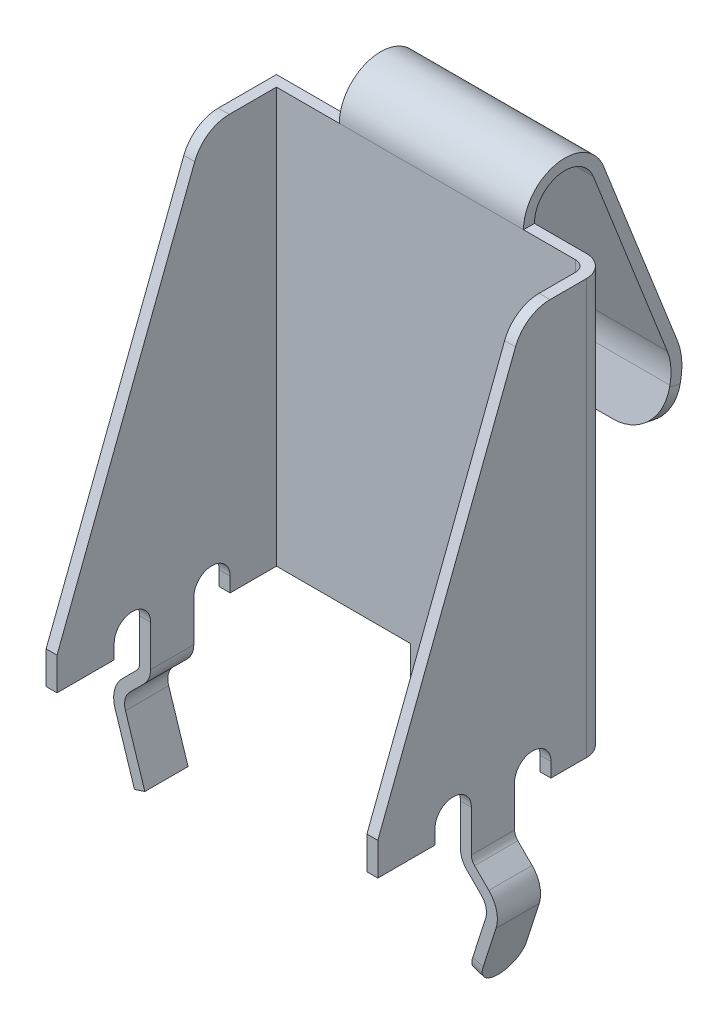
SolidWorks part; units mm, degrees
ref_plane "Front Plane" through (0, 0, 0) normal (0, 0, 1) x (1, 0, 0)
ref_plane "Top Plane" through (0, 0, 0) normal (0, 1, 0) x (1, 0, 0)
ref_plane "Right Plane" through (0, 0, 0) normal (1, 0, 0) x (0, 0, -1)
sketch "Sketch1" plane through (0, 0, 0) normal (0, 1, 0) x (1, 0, 0)
  line L1 (4.565, 0.15) -> (-4.565, 0.15)
  line L2 (4.565, 0.15) -> (4.565, -0.15)
  line L3 (4.565, -0.15) -> (-4.565, -0.15)
  line L4 (-4.565, 0.15) -> (-4.565, -0.15)
  line L5 (4.565, 0.15) -> (-4.565, -0.15) construction
  line L6 (4.565, -0.15) -> (-4.565, 0.15) construction
  point P0 (0, 0)
  dimension "D1" = 0.3
  dimension "D2" = 9.13
extrude "Boss-Extrude1" add sketch "Sketch1" along normal blind 11.42
sketch "Sketch2" plane through (0, 0, 0) normal (1, 0, 0) x (0, 0, -1)
  line L0 (-0.15, 11.42) -> (0.15, 11.42)
  line L1 (1.7718, 11.7271) -> (3.8061, 6.5484)
  line L2 (2.0511, 11.8368) -> (4.0854, 6.6581)
  line L3 (3.8797, 5.7002) -> (3.6104, 4.38)
  line L4 (3.6104, 4.38) -> (3.9044, 4.32)
  line L5 (3.9044, 4.32) -> (4.1737, 5.6403)
  line L6 (0.15, 11.42) -> (0.15, 0) construction
  line L7 (-0.15, 11.42) -> (-0.15, 0) construction
  line L8 (-0.15, 12.56) -> (2.8616, 12.56) construction
  line L9 (4.21, 11.1436) -> (4.21, 7.449) construction
  arc A0 (0.15, 11.42) -> (1.7718, 11.7271) centre (0.99, 11.42) cw
  arc A1 (-0.15, 11.42) -> (2.0511, 11.8368) centre (0.99, 11.42) cw
  arc A2 (3.8061, 6.5484) -> (3.8797, 5.7002) centre (2.41, 6) cw
  arc A3 (4.0854, 6.6581) -> (4.1737, 5.6403) centre (2.41, 6) cw
  point P9 (4.0992, 5.7403)
  point P22 (1.7542, 11.7687)
  point P25 (3.8176, 7.449)
  point P27 (3.8033, 6.4934)
  point P28 (0, 0)
  point P29 (3.9044, 6.1297)
  point P30 (0, 0)
  point P31 (0, 0)
  point P32 (0, 0)
  dimension "D1" = 1.14
  dimension "D5" = 1.5
  dimension "D2" = 4.06
  dimension "D3" = 4.32
  dimension "D4" = 6
extrude "Boss-Extrude2" add sketch "Sketch2" along normal mid plane 5.07
fillet "Fillet1" radius 1.3 2 edges at (-2.535, 4.35, -3.7574) (2.535, 4.35, -3.7574)
sketch "Sketch3" plane through (0, 0, -0.15) normal (0, 0, -1) x (-1, 0, 0)
  line L0 (-0.57, 0) -> (0.57, 0)
  line L1 (-4.565, 0) -> (4.565, 0) construction
  line L2 (0.57, 0) -> (0.57, -1.6)
  line L3 (0.57, -1.6) -> (0.33, -2.7708)
  line L4 (-0.57, 0) -> (-0.57, -1.6)
  line L5 (-0.57, -1.6) -> (-0.33, -2.7708)
  arc A0 (-0.33, -2.7708) -> (0.33, -2.7708) centre (0, -2.7031) ccw
  point P3 (-0.57, -1.5246)
  point P6 (0, 0)
  point P12 (0, -3.04)
  point P13 (0.57, -1.5959)
  point P14 (0.2485, -2.812)
  point P15 (0, 0)
  point P16 (0, 0)
  point P17 (0, 0)
  point P18 (0, 0)
  point P19 (-0.57, -1.6758)
  point P20 (0.332, -2.7687)
  dimension "D1" = 1.14
  dimension "D2" = 3.04
  dimension "D3" = 1.6
  dimension "D4" = 0.66
extrude "Boss-Extrude3" add sketch "Sketch3" against normal up to surface (0.3 mm away) up to face at (0, 7.6133, 0.15)
sketch "Sketch4" plane through (4.565, 0, 0) normal (1, 0, 0) x (0, 0, -1)
  line L0 (-0.15, 11.42) -> (-0.15, 0)
  line L1 (-0.15, 0) -> (-1.425, 0)
  line L2 (-0.15, 11.42) -> (-1.45, 11.42)
  line L3 (-2.4, 10.7672) -> (-6.19, 0.9)
  line L4 (-6.19, 0.9) -> (-6.19, 0)
  line L5 (-3.615, 0) -> (-2.425, 0)
  line L6 (-1.425, 0) -> (-1.425, 0.4)
  line L7 (-2.425, 0.4) -> (-2.425, 0)
  line L8 (-3.615, 0) -> (-3.615, 0.4)
  line L9 (-4.615, 0.4) -> (-4.615, 0)
  line L10 (-4.615, 0) -> (-6.19, 0)
  line L11 (0.15, 11.42) -> (0.15, 0) construction
  arc A0 (-1.45, 11.42) -> (-2.4, 10.7672) centre (-1.45, 10.4023) ccw
  arc A1 (-1.425, 0.4) -> (-2.425, 0.4) centre (-1.925, 0.4) ccw
  arc A2 (-3.615, 0.4) -> (-4.615, 0.4) centre (-4.115, 0.4) ccw
  point P9 (-3.02, 0)
  point P11 (0, 0)
  point P20 (-1.425, 0.4)
  point P24 (-5.8578, 0.0655)
  point P27 (-6.19, 1.692)
  point P28 (-4.115, 0.9)
  point P29 (-1.4501, 11.42)
  point P30 (-6.19, 0.9)
  point P31 (-3.615, 0.4)
  point P32 (-4.615, 0)
  point P33 (0, 0)
  point P34 (-4.115, 0.4)
  point P35 (-3.615, 0)
  point P36 (-3.615, 0.4)
  point P37 (-1.425, 0.4)
  point P38 (-1.45, 11.42)
  point P39 (-6.19, 0.9)
  point P40 (-4.615, 0)
  point P41 (-4.615, 0.4)
  point P42 (-3.615, 0.4)
  point P43 (-2.425, 0.4)
  point P44 (-1.425, 0.4)
  point P45 (-2.425, 0)
  point P46 (-3.615, 0)
  point P47 (-1.45, 11.42)
  dimension "D1" = 3.17
  dimension "D3" = 1
  dimension "D5" = 6.34
  dimension "D2" = 1.19
  dimension "D4" = 0.4
  dimension "D6" = 1.3
  dimension "D7" = 2.25
extrude "Boss-Extrude4" add sketch "Sketch4" against normal blind 0.3
fillet "Fillet2" radius 0.3 1 edges at (4.265, 5.71, 0.15)
fillet "Fillet3" radius 0.6 1 edges at (4.565, 5.71, -0.15)
ref_plane "Plane1" through (0, 0, 3.02) normal (0, 0, -1) x (-1, 0, 0)
sketch "Sketch5" plane through (0, 0, 3.02) normal (0, 0, -1) x (-1, 0, 0)
  line L0 (-4.565, 0) -> (-4.265, 0)
  line L1 (-4.565, 0) -> (-4.565, -0.7344)
  line L2 (-4.265, 0) -> (-4.265, -0.7344)
  line L3 (-4.6529, -0.9465) -> (-5.0457, -1.3393)
  line L4 (-4.4407, -1.1586) -> (-4.8336, -1.5514)
  line L5 (-5.2416, -2.1499) -> (-4.7078, -3.81)
  line L6 (-4.7078, -3.81) -> (-4.4222, -3.7182)
  line L7 (-4.4222, -3.7182) -> (-4.956, -2.0581)
  line L8 (-5.28, -1.8087) -> (-5.28, -4.8094) construction
  arc A0 (-4.565, -0.7344) -> (-4.6529, -0.9465) centre (-4.865, -0.7344) cw
  arc A1 (-4.265, -0.7344) -> (-4.4407, -1.1586) centre (-4.865, -0.7344) cw
  arc A2 (-4.8336, -1.5514) -> (-4.956, -2.0581) centre (-4.48, -1.905) ccw
  arc A3 (-5.0457, -1.3393) -> (-5.2416, -2.1499) centre (-4.48, -1.905) ccw
  point P18 (-6.7711, -4.8105)
  point P19 (-5.8095, -4.561)
  point P20 (-6.4267, -4.8094)
  point P23 (-4.565, -3.7641)
  point P24 (-4.6884, -0.8613)
  point P25 (-5.1532, -4.6483)
  point P26 (-4.7917, -1.8797)
  point P28 (-4.6126, -1.6359)
  point P29 (-4.565, -0.4629)
  point P30 (0, 0)
  point P31 (-4.6357, -0.8488)
  point P32 (-4.6464, -0.9142)
  dimension "D1" = 5.28
  dimension "D4" = 0.5
  dimension "D5" = 0.3
  dimension "D2" = 3.81
  dimension "D3" = 1.905
  dimension "D6" = 45
extrude "Boss-Extrude5" add sketch "Sketch5" along normal up to surface and the other way up to surface up to face at (4.415, 0.2, 2.425) other way up to face at (4.415, 0.2, 3.615)
fillet "Fillet4" radius 0.595 2 edges at (4.565, -3.7641, 3.615) (4.565, -3.7641, 2.425)
mirror "Mirror1" about plane through (0, 0, 0) normal (1, 0, 0) of "Boss-Extrude5", "Boss-Extrude4"
